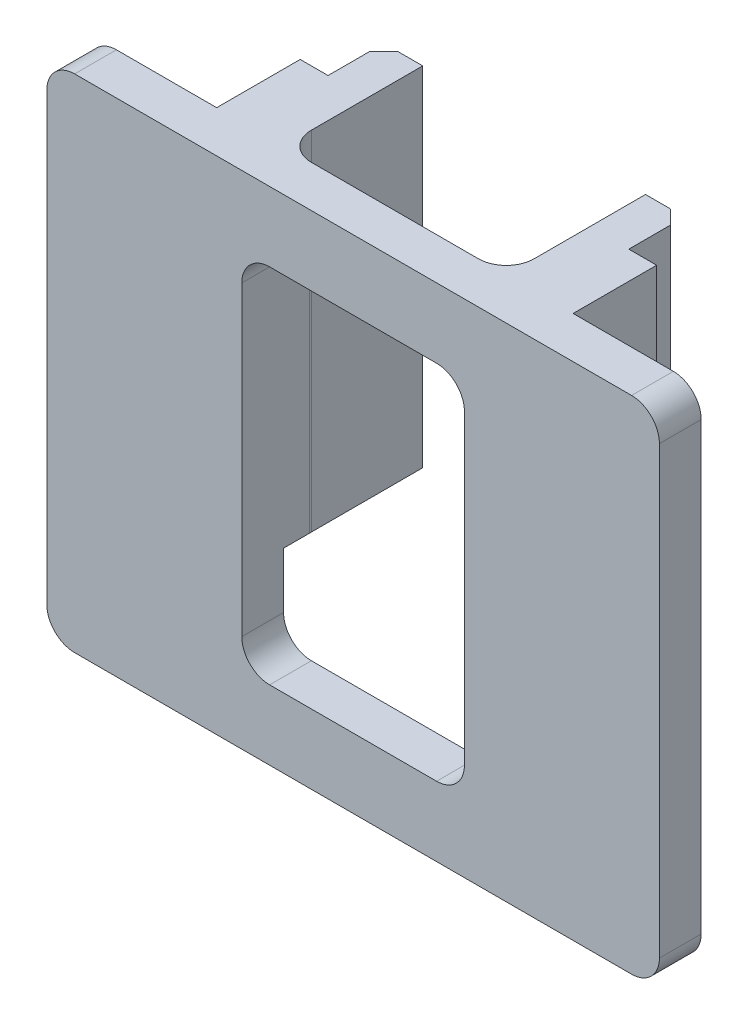
SolidWorks part; units mm, degrees
ref_plane "正面" through (0, 0, 0) normal (0, 0, 1) x (1, 0, 0)
ref_plane "平面" through (0, 0, 0) normal (0, 1, 0) x (1, 0, 0)
ref_plane "右側面" through (0, 0, 0) normal (1, 0, 0) x (0, 0, -1)
sketch "ｽｹｯﾁ1" plane through (0, 0, 0) normal (0, 0, 1) x (1, 0, 0)
  line L1 (-10.8, 12.5) -> (10.8, 12.5)
  line L2 (-10.8, 12.5) -> (-10.8, -12.5)
  line L3 (-10.8, -12.5) -> (10.8, -12.5)
  line L4 (10.8, 12.5) -> (10.8, -12.5)
  line L5 (-10.8, 12.5) -> (10.8, -12.5) construction
  line L6 (-10.8, -12.5) -> (10.8, 12.5) construction
  point P0 (0, 0)
  dimension "D1" = 21.6
  dimension "D2" = 25
extrude "ﾎﾞｽ - 押し出し1" add sketch "ｽｹｯﾁ1" along normal blind 10
sketch "ｽｹｯﾁ2" plane through (0, 0, 10) normal (0, 0, 1) x (1, 0, 0)
  line L0 (0, 12.5) -> (0, -12.5) construction
  line L1 (10.8, 12.5) -> (-10.8, 12.5) construction
  line L2 (-10.8, -12.5) -> (10.8, -12.5) construction
  line L4 (-22, 12.5) -> (22, 12.5)
  line L5 (-22, 12.5) -> (-22, -23.5)
  line L6 (-22, -23.5) -> (22, -23.5)
  line L7 (22, 12.5) -> (22, -23.5)
  line L8 (-22, 12.5) -> (22, -23.5) construction
  line L9 (-22, -23.5) -> (22, 12.5) construction
  point P6 (0, -5.5)
  dimension "D1" = 36
  dimension "D2" = 44
extrude "ﾎﾞｽ - 押し出し2" add sketch "ｽｹｯﾁ2" along normal blind 3
sketch "ｽｹｯﾁ3" plane through (10.8, 0, 0) normal (1, 0, 0) x (0, 0, -1)
  line L0 (-10, -12.5) -> (-10, 12.5) construction
  line L1 (-10, -12.5) -> (-4, -12.5)
  line L2 (-10, -12.5) -> (-10, 12.5)
  line L3 (-10, 12.5) -> (-4, 12.5)
  line L4 (-4, -12.5) -> (-4, 12.5)
  line L5 (-10, -23.5) -> (-10, 12.5) construction
  line L6 (-10, 12.5) -> (0, 12.5) construction
  dimension "D1" = 6
extrude "ﾎﾞｽ - 押し出し3" add sketch "ｽｹｯﾁ3" along normal blind 2 and the other way blind 23.6
chamfer "面取り1" distance 1 angle 45 2 edges at (10.8, 0, 0) (-10.8, 0, 0)
sketch "ｽｹｯﾁ4" plane through (0, 0, 0) normal (0, 0, -1) x (-1, 0, 0)
  line L0 (-9.8, 12.5) -> (9.8, 12.5) construction
  line L1 (-8, 12.5) -> (8, 12.5)
  line L2 (-8, 12.5) -> (-8, -12.5)
  line L3 (-8, -12.5) -> (8, -12.5)
  line L4 (8, 12.5) -> (8, -12.5)
  line L5 (-8, 12.5) -> (8, -12.5) construction
  line L6 (-8, -12.5) -> (8, 12.5) construction
  line L8 (0, 0) -> (0, 15.3034) construction
  line L9 (9.8, -12.5) -> (-9.8, -12.5) construction
  point P0 (0, 0)
  point P12 (0, 0)
  dimension "D2" = 16
extrude "ｶｯﾄ - 押し出し1" cut sketch "ｽｹｯﾁ4" against normal up to surface (10 mm away) up to face at (0, -2.75, 10)
fillet "ﾌｨﾚｯﾄ1" radius 2 4 edges at (22, 12.5, 11.5) (22, -23.5, 11.5) (-22, -23.5, 11.5) (-22, 12.5, 11.5)
sketch "ｽｹｯﾁ5" plane through (0, 0, 10) normal (0, 0, -1) x (-1, 0, 0)
  line L0 (8, 12.5) -> (-8, 12.5) construction
  line L1 (-7.9956, 7.5) -> (7.9956, 7.5)
  line L2 (-7.9956, 7.5) -> (-7.9956, -18.5)
  line L3 (-7.9956, -18.5) -> (7.9956, -18.5)
  line L4 (7.9956, 7.5) -> (7.9956, -18.5)
  line L5 (-7.9956, 7.5) -> (7.9956, -18.5) construction
  line L6 (-7.9956, -18.5) -> (7.9956, 7.5) construction
  line L7 (20, -23.5) -> (-20, -23.5) construction
  point P0 (0, -5.5)
  dimension "D1" = 5
  dimension "D2" = 5
extrude "ｶｯﾄ - 押し出し2" cut sketch "ｽｹｯﾁ5" against normal through all
fillet "ﾌｨﾚｯﾄ2" radius 2 4 edges at (-7.9956, -18.5, 11.5) (7.9956, -18.5, 11.5) (-7.9956, 7.5, 11.5) (7.9956, 7.5, 11.5)
fillet "ﾌｨﾚｯﾄ3" radius 2 2 edges at (8, 0, 10) (-8, 0, 10)
